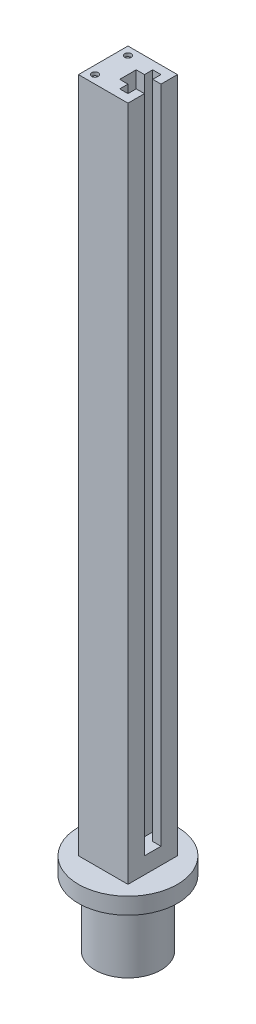
SolidWorks part; units mm, degrees
ref_plane "Front Plane" through (0, 0, 0) normal (0, 0, 1) x (1, 0, 0)
ref_plane "Top Plane" through (0, 0, 0) normal (0, 1, 0) x (1, 0, 0)
ref_plane "Right Plane" through (0, 0, 0) normal (1, 0, 0) x (0, 0, -1)
other "Center of Mass"
sketch "Sketch4" plane through (0, 0, 0) normal (0, 0, 1) x (1, 0, 0)
  line L0 (0, -148.1481) -> (100, -148.1481)
  line L1 (100, -148.1481) -> (100, 51.8519)
  line L2 (100, 51.8519) -> (150, 51.8519)
  line L3 (150, 51.8519) -> (150, 101.8519)
  line L4 (150, 101.8519) -> (0, 101.8519)
  line L5 (0, 101.8519) -> (0, -148.1481)
  dimension "D1" = 100
  dimension "D2" = 50
  dimension "D3" = 50
  dimension "D4" = 250
revolve "Revolve1" add sketch "Sketch4" angle 360 about L5 region at (56.8182, -14.0572, 0)
sketch "Sketch5" plane through (0, 101.8519, 0) normal (0, 1, 0) x (1, 0, 0)
  line L1 (-75, 75) -> (75, 75)
  line L2 (-75, 75) -> (-75, -75)
  line L3 (-75, -75) -> (75, -75)
  line L4 (75, 75) -> (75, -75)
  line L5 (-75, 75) -> (75, -75) construction
  line L6 (-75, -75) -> (75, 75) construction
  point P0 (0, 0)
  dimension "D1" = 150
  dimension "l" = 150
extrude "Boss-Extrude1" add sketch "Sketch5" along normal blind 2050 contours L2 L1 L4 L3
sketch "Sketch6" plane through (0, 2151.8519, 0) normal (0, 1, 0) x (1, 0, 0)
  line L0 (0, 0) -> (0, 25)
  line L1 (0, 25) -> (25, 25)
  line L2 (25, 25) -> (25, 50)
  line L3 (25, 50) -> (50, 50)
  line L4 (50, 50) -> (50, 25)
  line L5 (50, 25) -> (75, 25)
  line L6 (75, 75) -> (75, -75) construction
  line L7 (75, 25) -> (75, -25)
  line L8 (75, -25) -> (50, -25)
  line L9 (50, -25) -> (50, -50)
  line L10 (50, -50) -> (25, -50)
  line L11 (25, -50) -> (25, -25)
  line L12 (25, -25) -> (0, -25)
  line L13 (0, -25) -> (0, 0)
  point P6 (62.5, 25)
  dimension "D1" = 25
  dimension "D2" = 25
  dimension "D3" = 25
  dimension "D4" = 25
  dimension "D5" = 25
  dimension "D6" = 25
  dimension "D7" = 25
  dimension "D8" = 25
  dimension "D9" = 25
  dimension "D10" = 25
extrude "Cut-Extrude1" cut sketch "Sketch6" against normal blind 2000 contours L13 L0 L1 L2 L3 L4 L5 L7 L8 L9 L10 L11 L12
sketch "Sketch8" plane through (0, 2151.8519, 0) normal (0, 1, 0) x (1, 0, 0)
  line L0 (-137.5, 0) -> (137.5, 0) construction
  circle A1 centre (-50, 50) radius 10
  circle A2 centre (-50, -50) radius 10
  dimension "D1" = 50
  dimension "D2" = 50
extrude "Cut-Extrude2" cut sketch "Sketch8" against normal blind 10
ref_axis "Link_1_Axis" through (0, -148.1481, 0) along (0, 1, 0)
